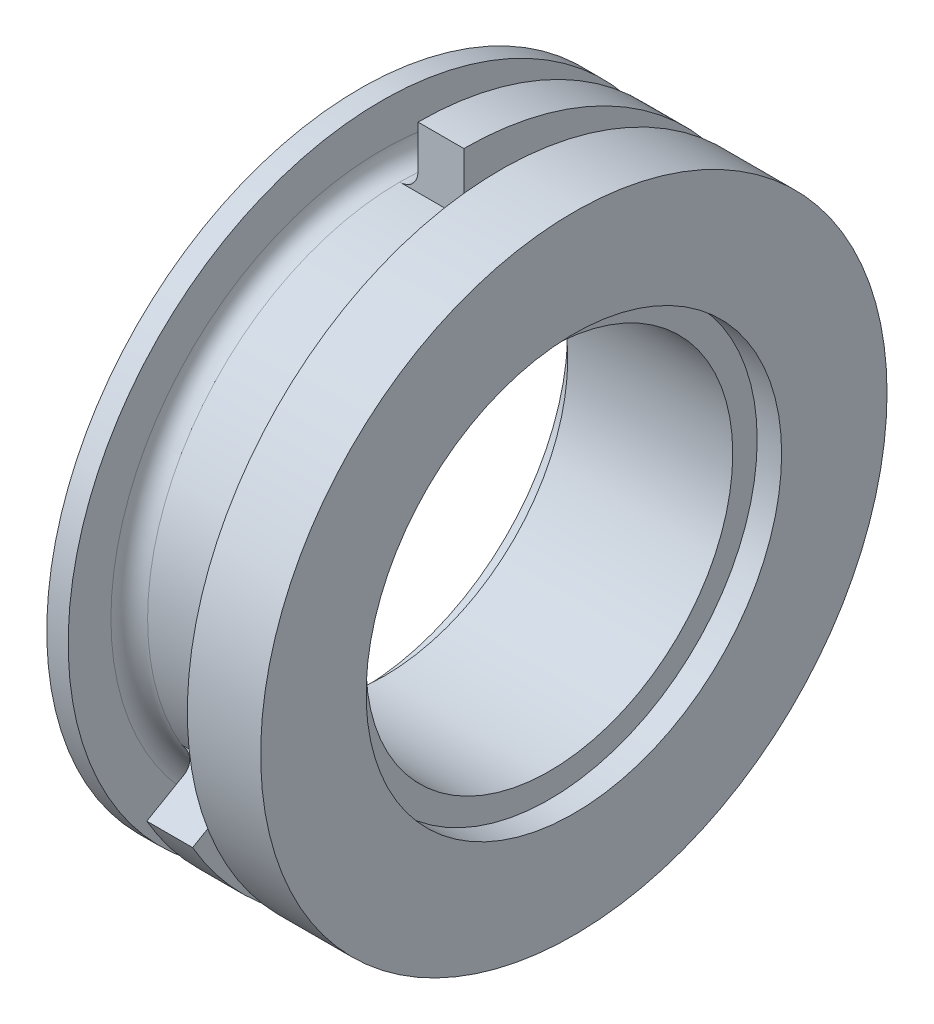
SolidWorks part; units mm, degrees
ref_plane "Front Plane" through (0, 0, 0) normal (0, 0, 1) x (1, 0, 0)
ref_plane "Top Plane" through (0, 0, 0) normal (0, 1, 0) x (1, 0, 0)
ref_plane "Right Plane" through (0, 0, 0) normal (1, 0, 0) x (0, 0, -1)
sketch "Sketch2" plane through (0, 0, 0) normal (0, 1, 0) x (1, 0, 0)
  line L1 (0, 6) -> (7, 6)
  line L3 (7, 0) -> (0, 0)
  line L4 (0, 6) -> (0, 10.25)
  line L5 (0, 10.25) -> (0.7, 10.25)
  line L6 (0.7, 10.25) -> (0.7, 8.25)
  line L7 (0.7, 8.25) -> (1.9, 8.25)
  line L8 (1.9, 8.25) -> (1.9, 10.25)
  line L9 (1.9, 10.25) -> (3.4, 10.25)
  line L10 (3.4, 10.25) -> (3.4, 8.25)
  line L11 (3.4, 8.25) -> (4.6, 8.25)
  line L12 (4.6, 8.25) -> (4.6, 10.25)
  line L13 (4.6, 10.25) -> (7, 10.25)
  line L14 (7, 10.25) -> (7, 6)
  point P13 (4, 8.25)
  dimension "D1" = 6
  dimension "D2" = 7
  dimension "D3" = 8.25
  dimension "D4" = 1.2
  dimension "D5" = 1.2
  dimension "D6" = 1.5
  dimension "D7" = 3
  dimension "D8" = 2
revolve "Revolve1" add sketch "Sketch2" angle 360 about L3 region at (3.6635, 0, -7.9086)
ref_plane "Plane1" through (0, 10, 0) normal (0, 1, 0) x (1, 0, 0)
sketch "Sketch8" plane through (0, 0, 0) normal (0, 0, 1) x (1, 0, 0)
  line L0 (3.4, -8.25) -> (3.4, 8.25) construction
  line L1 (3.4, -10.25) -> (3.4, 10.25) construction
  line L2 (1.9, 8.25) -> (1.9, -8.25) construction
  line L3 (1.9, 10.25) -> (1.9, -10.25) construction
  line L4 (3.4, -8.25) -> (3.4, 8.25) construction
  line L5 (3.4, -10.25) -> (3.4, 10.25) construction
  line L6 (1.9, 8.25) -> (1.9, -8.25) construction
  line L7 (1.9, 10.25) -> (1.9, -10.25) construction
  line L8 (0, 0) -> (1.9, 0) construction
  line L9 (1.9, 10.25) -> (3.4, 10.25)
  line L10 (1.9, 10.25) -> (1.9, 8.25)
  line L11 (1.9, 8.25) -> (3.4, 8.25)
  line L12 (3.4, 10.25) -> (3.4, 8.25)
revolve "Cut-Revolve1" cut sketch "Sketch8" angle 120 about L8
sketch "Sketch7" plane through (0, 10, 0) normal (0, 1, 0) x (1, 0, 0)
  line L0 (4.6, 8.25) -> (4.6, -8.25) construction
  line L1 (0.7, -8.25) -> (0.7, 8.25) construction
  line L2 (3.4, -7.1447) -> (3.4, 8.25) construction
  line L3 (1.9, 8.25) -> (1.9, -7.1447) construction
  line L4 (4.6, 8.25) -> (4.6, -8.25) construction
  line L5 (0.7, -8.25) -> (0.7, 8.25) construction
  line L6 (3.4, -7.1447) -> (3.4, 8.25) construction
  line L7 (1.9, 8.25) -> (1.9, -7.1447) construction
  line L9 (1.9, -4) -> (3.4, -4)
  line L10 (1.9, -4) -> (1.9, 4)
  line L11 (1.9, 4) -> (3.4, 4)
  line L12 (3.4, -4) -> (3.4, 4)
  point P12 (1.9, 0)
  dimension "D1" = 8
fillet "Fillet1" radius 0.6 4 edges at (4.6, 0, -8.25) (3.4, -4.125, -7.1447) (1.9, -4.125, -7.1447) (0.7, 0, -8.25)
sketch "Sketch3" plane through (7, 0, 0) normal (1, 0, 0) x (0, 0, -1)
  circle A0 centre (0, 0) radius 6.8
  dimension "D1" = 13.6
extrude "Cut-Extrude1" cut sketch "Sketch3" against normal blind 0.8
sketch "Sketch4" plane through (0, 0, 0) normal (-1, 0, 0) x (0, 0, 1)
  circle A0 centre (0, 0) radius 6.8 construction
  circle A1 centre (0, 0) radius 6.8
extrude "Cut-Extrude2" cut sketch "Sketch4" against normal blind 0.8
fillet "Fillet2" [suppressed] radius 0.5
